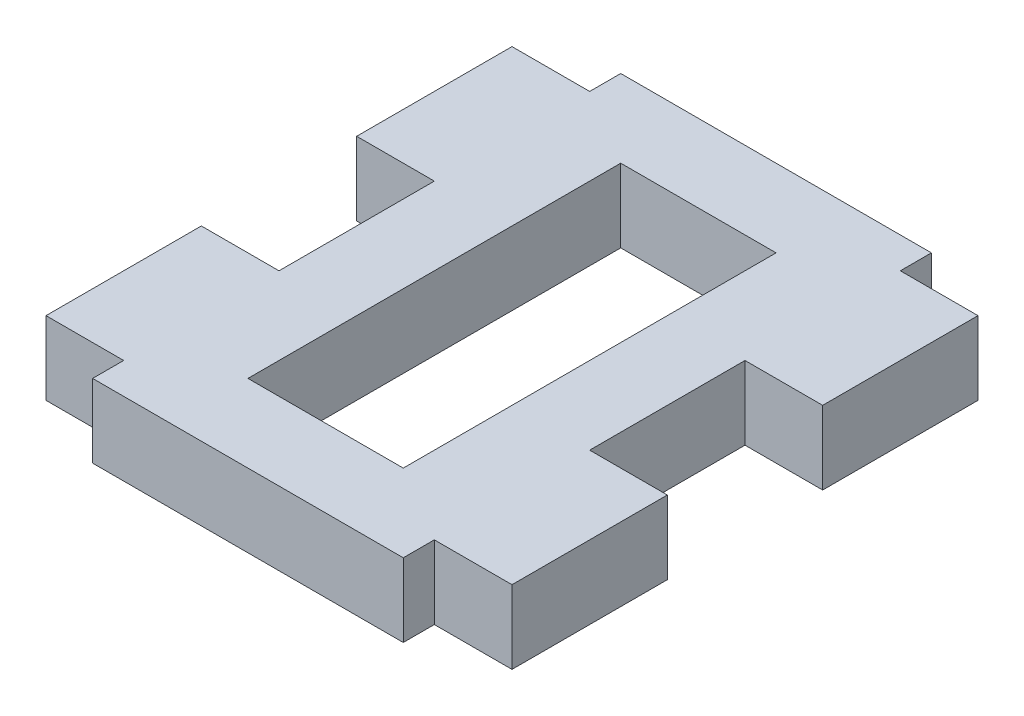
SolidWorks part; units mm, degrees
ref_plane "Front Plane" through (0, 0, 0) normal (0, 0, 1) x (1, 0, 0)
ref_plane "Top Plane" through (0, 0, 0) normal (0, 1, 0) x (1, 0, 0)
ref_plane "Right Plane" through (0, 0, 0) normal (1, 0, 0) x (0, 0, -1)
sketch "Sketch1" plane through (0, 0, 0) normal (0, 1, 0) x (1, 0, 0)
  line L1 (-12.7, -21.59) -> (12.7, -21.59)
  line L2 (-12.7, -21.59) -> (-12.7, 21.59)
  line L3 (-12.7, 21.59) -> (12.7, 21.59)
  line L4 (12.7, -21.59) -> (12.7, 21.59)
  line L5 (-12.7, -21.59) -> (12.7, 21.59) construction
  line L6 (-12.7, 21.59) -> (12.7, -21.59) construction
  point P0 (0, 0)
  dimension "D1" = 25.4
  dimension "D2" = 43.18
extrude "Boss-Extrude1" add sketch "Sketch1" along normal blind 6
sketch "Sketch2" plane through (0, 0, 0) normal (0, -1, 0) x (1, 0, 0)
  line L0 (-12.7, 19.05) -> (-19.05, 19.05)
  line L1 (-12.7, -21.59) -> (-12.7, 21.59) construction
  line L2 (-19.05, 19.05) -> (-19.05, 6.35)
  line L3 (-19.05, 6.35) -> (-12.7, 6.35)
  line L4 (-12.7, 6.35) -> (-12.7, 19.05)
  line L5 (-12.7, 0) -> (12.7, 0) construction
  line L6 (12.7, 21.59) -> (12.7, -21.59) construction
  line L7 (0, -21.59) -> (0, 21.59) construction
  line L8 (-12.7, 21.59) -> (12.7, 21.59) construction
  line L9 (12.7, 6.35) -> (12.7, 19.05)
  line L10 (19.05, 6.35) -> (12.7, 6.35)
  line L11 (19.05, 19.05) -> (19.05, 6.35)
  line L12 (12.7, 19.05) -> (19.05, 19.05)
  line L13 (12.7, -19.05) -> (19.05, -19.05)
  line L14 (19.05, -19.05) -> (19.05, -6.35)
  line L15 (19.05, -6.35) -> (12.7, -6.35)
  line L16 (12.7, -6.35) -> (12.7, -19.05)
  line L17 (-12.7, -6.35) -> (-12.7, -19.05)
  line L18 (-19.05, -6.35) -> (-12.7, -6.35)
  line L19 (-19.05, -19.05) -> (-19.05, -6.35)
  line L20 (-12.7, -19.05) -> (-19.05, -19.05)
  point P12 (0, 0)
  point P18 (0, 0)
  dimension "D1" = 12.7
  dimension "D2" = 6.35
  dimension "D3" = 6.35
extrude "Boss-Extrude2" add sketch "Sketch2" against normal up to surface (6 mm away) up to face at (0, 6, 0)
sketch "Sketch3" plane through (0, 0, 0) normal (0, -1, 0) x (1, 0, 0)
  line L0 (-12.7, 21.59) -> (12.7, 21.59) construction
  line L1 (-6.35, -15.24) -> (6.35, -15.24)
  line L2 (-6.35, -15.24) -> (-6.35, 15.24)
  line L3 (-6.35, 15.24) -> (6.35, 15.24)
  line L4 (6.35, -15.24) -> (6.35, 15.24)
  line L5 (-6.35, -15.24) -> (6.35, 15.24) construction
  line L6 (-6.35, 15.24) -> (6.35, -15.24) construction
  line L7 (12.7, 6.35) -> (12.7, -6.35) construction
  point P0 (0, 0)
  dimension "D1" = 6.35
  dimension "D2" = 6.35
extrude "Cut-Extrude1" cut sketch "Sketch3" against normal through all
